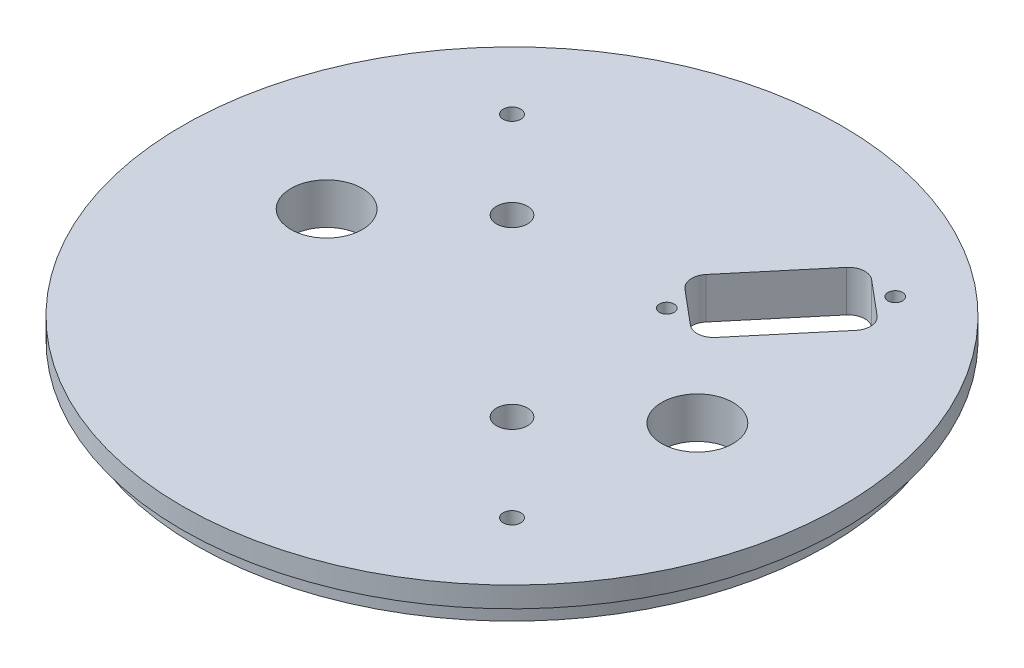
SolidWorks part; units mm, degrees
material "6061-T6 (SS)"
ref_plane "Front Plane" through (0, 0, 0) normal (0, 0, 1) x (1, 0, 0)
ref_plane "Top Plane" through (0, 0, 0) normal (0, 1, 0) x (1, 0, 0)
ref_plane "Right Plane" through (0, 0, 0) normal (1, 0, 0) x (0, 0, -1)
sketch "Sketch1" plane through (0, 0, 0) normal (0, 1, 0) x (1, 0, 0)
  line L0 (0, -50.8) -> (0, 50.8) construction
  line L1 (-50.8, 0) -> (50.8, 0) construction
  line L2 (-26.9408, 26.9408) -> (0, 0) construction
  line L3 (0, 56.7387) -> (0, 29.6936) construction
  line L4 (3.6407, 56.7387) -> (3.6407, 29.6936) construction
  line L5 (-3.6407, 56.7387) -> (-3.6407, 29.6936) construction
  line L6 (0, -56.7387) -> (0, -29.6936) construction
  line L7 (3.6407, -56.7387) -> (3.6407, -29.6936) construction
  line L8 (-3.6407, -56.7387) -> (-3.6407, -29.6936) construction
  line L9 (-35.921, -35.921) -> (54.3236, 54.3236) construction
  circle A0 centre (0, 0) radius 50.8
  circle A1 centre (0, 0) radius 3.175 construction
  circle A2 centre (28.575, 0) radius 5.5
  circle A3 centre (-28.575, 0) radius 5.5
  circle A4 centre (-26.9408, 26.9408) radius 1.3589
  arc A6 (3.6407, 56.7387) -> (-3.6407, 56.7387) centre (0, 56.7387) ccw construction
  arc A7 (-3.6407, 29.6936) -> (3.6407, 29.6936) centre (0, 29.6936) ccw construction
  arc A8 (3.6407, -56.7387) -> (-3.6407, -56.7387) centre (0, -56.7387) cw construction
  arc A9 (-3.6407, -29.6936) -> (3.6407, -29.6936) centre (0, -29.6936) cw construction
  circle A10 centre (26.9408, -26.9408) radius 1.3589
  circle A11 centre (-13.4704, 13.4704) radius 2.3813
  circle A12 centre (13.4704, -13.4704) radius 2.3813
  point P16 (0, 43.2162)
  point P19 (0, 0)
  point P26 (0, -43.2162)
  dimension "D1" = 101.6
  dimension "D2" = 6.35
  dimension "D3" = 11
  dimension "D5" = 2.7178
  dimension "D8" = 4.7625
  dimension "D6" = 38.1
  dimension "D7" = 45
  dimension "D4" = 45
  dimension "D9" = 28.575
extrude "Boss-Extrude1" add sketch "Sketch1" along normal blind 6.35
sketch "Sketch2" plane through (0, 0, 0) normal (0, -1, 0) x (1, 0, 0)
  circle A0 centre (0, 0) radius 76.2
  circle A1 centre (0, 0) radius 48.641
  dimension "D1" = 152.4
  dimension "D2" = 97.282
extrude "Cut-Extrude1" cut sketch "Sketch2" against normal blind 3.175
sketch "Sketch3" plane through (0, 6.35, 0) normal (0, 1, 0) x (1, 0, 0)
  line L0 (0, 50.8) -> (0, -50.8) construction
  line L1 (-50.8, 0) -> (50.8, 0) construction
  line L2 (0, 34.798) -> (0, 13.97) construction
  line L3 (3.2385, 34.798) -> (3.2385, 13.97)
  line L4 (-3.2385, 34.798) -> (-3.2385, 13.97)
  line L5 (0, -34.798) -> (0, -13.97) construction
  line L6 (3.2385, -34.798) -> (3.2385, -13.97)
  line L7 (-3.2385, -34.798) -> (-3.2385, -13.97)
  circle A0 centre (0, 0) radius 50.8 construction
  arc A1 (3.2385, 34.798) -> (-3.2385, 34.798) centre (0, 34.798) ccw
  arc A2 (-3.2385, 13.97) -> (3.2385, 13.97) centre (0, 13.97) ccw
  arc A3 (3.2385, -34.798) -> (-3.2385, -34.798) centre (0, -34.798) cw
  arc A4 (-3.2385, -13.97) -> (3.2385, -13.97) centre (0, -13.97) cw
  point P7 (0, 13.97)
  point P8 (0, 34.798)
  point P12 (0, 24.384)
  point P20 (0, -24.384)
  point P25 (0, -34.798)
  point P26 (0, -13.97)
  dimension "D1" = 13.97
  dimension "D2" = 20.828
  dimension "D3" = 6.477
extrude "Cut-Extrude2" cut sketch "Sketch3" against normal blind 3.556 from offset 5.969 offset against normal yes
hole_wizard "Tap Drill for #4-40 Tap1" positions "Sketch5" profile "Sketch6" hole size "#4-40" standard "ANSI Inch" end condition through all
sketch "Sketch5" plane through (0, 6.35, 0) normal (0, 1, 0) x (1, 0, 0)
  line L0 (0, 0) -> (53.6567, 63.9455) construction
  line L2 (0, 0) -> (28.575, 0) construction
  point P0 (10.8845, 12.9717)
  point P2 (26.9542, 32.1228)
  dimension "D1" = 50
  dimension "D2" = 25
  dimension "D3" = 16.9333
sketch "Sketch6" plane through (10.8845, 6.35, -12.9717) normal (1, 0, 0) x (0, 0, 1)
  line L0 (0, 0) -> (0, 6.35)
  line L1 (0, 6.35) -> (1.1303, 6.35)
  line L2 (1.1303, 6.35) -> (1.1303, 0)
  line L5 (1.1303, 0) -> (0, 0)
  line L11 (0, -6.35) -> (0, 107.95) construction
  dimension "Thru Hole Dia." = 2.2606
  dimension "Thru Hole Depth" = 6.35
sketch "Sketch4" plane through (0, 6.35, 0) normal (0, 1, 0) x (1, 0, 0)
  line L0 (9.7272, 16.927) -> (14.9807, 12.5187)
  line L1 (9.4141, 20.5054) -> (19.2796, 32.2627)
  line L2 (18.5591, 12.8318) -> (28.4247, 24.5891)
  line L3 (22.858, 32.5757) -> (28.1116, 28.1675)
  line L4 (0, 0) -> (26.9542, 32.1228) construction
  circle A1 centre (10.8845, 12.9717) radius 1.1303 construction
  arc A2 (19.2796, 32.2627) -> (22.858, 32.5757) centre (21.2254, 30.63) cw
  arc A3 (28.4247, 24.5891) -> (28.1116, 28.1675) centre (26.4789, 26.2217) ccw
  arc A4 (14.9807, 12.5187) -> (18.5591, 12.8318) centre (16.6134, 14.4645) ccw
  arc A5 (9.4141, 20.5054) -> (9.7272, 16.927) centre (11.3599, 18.8727) ccw
  point P11 (12.3539, 14.7229)
  dimension "D4" = 2.54
  dimension "D1" = 2.286
  dimension "D2" = 2.286
  dimension "D3" = 11.938
extrude "Cut-Extrude3" cut sketch "Sketch4" against normal through all
equation "\"leadDist\"=1.5"
equation "\"Lead_Screw_Dist\" = 2.25in"
equation "\"D9@Sketch1\"=\"Lead_Screw_Dist\"/2"
equation "\"Lead_Screw_Diam\" = 11mm"
equation "\"D3@Sketch1\"=\"Lead_Screw_Diam\""
equation "\"Bodytube_OD\" = 6.17in"
equation "\"Bodytube_ID\" = 5.998in"
equation "\"Motor_OD\" = 4in"
equation "\"Fwd_Tube_Length\" = 40in"
equation "\"Mid_Tube_Length\" = 1in"
equation "\"Aft_Section_Length\"= 39in"
equation "\"AB_Coupler_OD_Length\"= 1in"
equation "\"AB_Coupling_Section_Length\"= 0.375in"
equation "\"AB_Coupler_Length\"= \"AB_Coupler_OD_Length\" + \"AB_Coupling_Section_Length\" * 2"
equation "\"Cutout_Angle\" = 80"
equation "\"AB_Paddle_Height\" = 0.375in"
equation "\"AB_Coupler_Num_Screws\"= 6"
equation "\"Num_Cutouts\" = 3"
equation "\"AB_Coupler_OD\"= 6.17in"
equation "\"AB_Coupler_ID\"= 5.75in"
equation "\"AB_Coupler_Surface_Diameter\"= 5.998in"
equation "\"AB_Coupling_Screw_Diameter\"= 0.1065in"
equation "\"AB_Central_Bushing_Length\" = .75in"
equation "\"Lead_Screw_Length\" = (\"Mid_Coupler_Length\" + 2*0.375in + 2*0.5in)"
equation "\"Paddle_Pin_Offset\" = .25in"
equation "\"Paddle_Pin_Radius\" = 2.25in"
equation "\"SS_Paddle_Pin_Radius\" = 2.25*0.66in"
equation "\"Paddle_Gear_OD\" = 3.2in"
equation "\"Drive_Gear_OD\" = 1.7in"
equation "\"Fwd_BKHD_From_Top\" = 18in"
equation "\"Fin_Thickness\"= .118in"
equation "\"Guiderail_Cutout_Diameter\"= 1.5in"
equation "\"DB9_Hole_Dist\" = 25mm"
equation "\"Airbrakes_Wire_Hole_Dia\" = .25in"
equation "\"Airbrakes_Wire_Hole_Dist\" = 1.1in"
equation "\"Servo_Gear_Offset\" = 0.5in"
equation "\"Mid_Coupler_Length\" = 13in"
equation "\"D2@Sketch5\"=\"DB9_Hole_Dist\""
equation "\"DB9_Relief_Width\" = 0.47in"
equation "\"DB9_Relief_Hole_Offset\" = 0.09in"
equation "\"D1@Sketch4\"=\"DB9_Relief_Hole_Offset\""
equation "\"D2@Sketch4\"=\"DB9_Relief_Hole_Offset\""
equation "\"D3@Sketch4\"=\"DB9_Relief_Width\""
